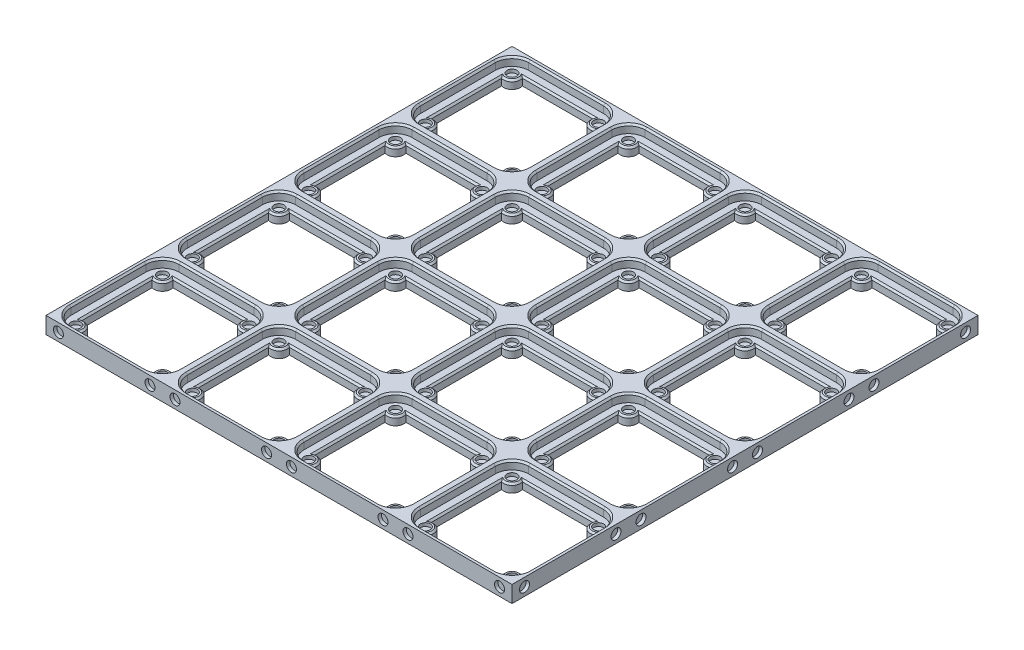
SolidWorks part; units mm, degrees
ref_plane "Front Plane" through (0, 0, 0) normal (0, 0, 1) x (1, 0, 0)
ref_plane "Top Plane" through (0, 0, 0) normal (0, 1, 0) x (1, 0, 0)
ref_plane "Right Plane" through (0, 0, 0) normal (1, 0, 0) x (0, 0, -1)
sketch "Sketch1" plane through (0, 0, 0) normal (0, 1, 0) x (1, 0, 0)
  line L1 (0, 0) -> (70, 0)
  line L2 (0, 0) -> (0, 70)
  line L3 (0, 70) -> (70, 70)
  line L4 (70, 0) -> (70, 70)
  dimension "D1" = 70
  dimension "D2" = 70
extrude "Boss-Extrude2" add sketch "Sketch1" along normal blind 7
sketch "Sketch3" plane through (0, 7, 0) normal (0, 1, 0) x (1, 0, 0)
  line L8 (2.5, 67.5) -> (2.5, 2.5)
  line L9 (2.5, 2.5) -> (67.5, 2.5)
  line L10 (67.5, 2.5) -> (67.5, 67.5)
  line L11 (67.5, 67.5) -> (2.5, 67.5)
  line L12 (2.5, 57.5) -> (2.5, 12.5)
  line L13 (12.5, 2.5) -> (57.5, 2.5)
  line L14 (67.5, 12.5) -> (67.5, 57.5)
  line L15 (57.5, 67.5) -> (12.5, 67.5)
  arc A0 (2.5, 12.5) -> (12.5, 2.5) centre (12.5, 12.5) ccw
  arc A1 (57.5, 2.5) -> (67.5, 12.5) centre (57.5, 12.5) ccw
  arc A2 (67.5, 57.5) -> (57.5, 67.5) centre (57.5, 57.5) ccw
  arc A3 (2.5, 57.5) -> (12.5, 67.5) centre (12.5, 57.5) cw
  dimension "D2" = 10
  dimension "D1" = 2.5
extrude "Cut-Extrude1" cut sketch "Sketch3" against normal blind 5
sketch "Sketch9" plane through (0, 0, 0) normal (0, -1, 0) x (1, 0, 0)
  line L1 (0, -70) -> (70, -70)
  line L2 (0, -70) -> (0, 0)
  line L3 (0, 0) -> (70, 0)
  line L4 (70, -70) -> (70, 0)
extrude "Boss-Extrude3" add sketch "Sketch9" along normal blind 5
sketch "Sketch20" plane through (0, 2, 0) normal (0, 1, 0) x (1, 0, 0)
  line L0 (35, 35) -> (8.9645, 61.0355) construction
  line L19 (12.5, 7.5) -> (57.5, 7.5)
  line L20 (62.5, 12.5) -> (62.5, 57.5)
  line L21 (57.5, 62.5) -> (12.5, 62.5)
  line L22 (7.5, 57.5) -> (7.5, 12.5)
  line L23 (13.7452, 7.5) -> (56.2548, 7.5)
  line L24 (62.5, 13.7452) -> (62.5, 56.2548)
  line L25 (56.2548, 62.5) -> (13.7452, 62.5)
  line L26 (7.5, 56.2548) -> (7.5, 13.7452)
  arc A0 (56.2548, 62.5) -> (62.5, 56.2548) centre (61.0355, 61.0355) ccw
  arc A1 (62.5, 13.7452) -> (56.2548, 7.5) centre (61.0355, 8.9645) ccw
  arc A2 (13.7452, 7.5) -> (7.5, 13.7452) centre (8.9645, 8.9645) ccw
  circle A4 centre (8.9645, 61.0355) radius 3
  circle A5 centre (8.9645, 8.9645) radius 3
  circle A6 centre (61.0355, 8.9645) radius 3
  circle A7 centre (61.0355, 61.0355) radius 3
  arc A21 (7.5, 56.2548) -> (13.7452, 62.5) centre (8.9645, 61.0355) ccw
  arc A24 (7.5, 12.5) -> (12.5, 7.5) centre (12.5, 12.5) ccw
  arc A25 (57.5, 7.5) -> (62.5, 12.5) centre (57.5, 12.5) ccw
  arc A26 (62.5, 57.5) -> (57.5, 62.5) centre (57.5, 57.5) ccw
  arc A27 (12.5, 62.5) -> (7.5, 57.5) centre (12.5, 57.5) ccw
  point P8 (35, 35)
  dimension "D2" = 6
  dimension "D3" = 4
  dimension "D4" = 36.8198
  dimension "D1" = 5
extrude "Cut-Extrude11" cut sketch "Sketch20" against normal through all contours L23 A1 L24 A0 L25 A21 L26 A2
sketch "Sketch21" plane through (0, 2, 0) normal (0, 1, 0) x (1, 0, 0)
  circle A0 centre (8.9645, 61.0355) radius 3
  circle A1 centre (61.0355, 61.0355) radius 3
  circle A2 centre (61.0355, 8.9645) radius 3
  circle A3 centre (8.9645, 8.9645) radius 3
extrude "Cut-Extrude12" cut sketch "Sketch21" against normal blind 2 contours A0 | A1 | A2 | A3
chamfer "Chamfer3" distance 1 angle 45 16 edges at (35, 7, -2.5) (64.5711, 7, -5.4289) (5.4289, 7, -5.4289) (67.5, 7, -35) (2.5, 7, -35) (64.5711, 7, -64.5711) (5.4289, 7, -64.5711) (35, 7, -67.5) (12.5, 2, -12.5) (35, 2, -7.5) (57.5, 2, -12.5) (62.5, 2, -35) (57.5, 2, -57.5) (7.5, 2, -35) (12.5, 2, -57.5) (35, 2, -62.5)
sketch "Sketch22" plane through (0, -5, 0) normal (0, -1, 0) x (1, 0, 0)
  line L0 (7.5, -13.7452) -> (7.5, -56.2548)
  line L1 (0, 0) -> (70, 0)
  line L2 (0, 0) -> (0, -70)
  line L3 (0, -70) -> (70, -70)
  line L4 (70, 0) -> (70, -70)
  line L6 (13.7452, -62.5) -> (56.2548, -62.5)
  line L8 (62.5, -56.2548) -> (62.5, -13.7452)
  line L10 (56.2548, -7.5) -> (13.7452, -7.5)
  arc A0 (7.5, -13.7452) -> (13.7452, -7.5) centre (8.9645, -8.9645) ccw
  arc A1 (56.2548, -7.5) -> (62.5, -13.7452) centre (61.0355, -8.9645) ccw
  arc A2 (62.5, -56.2548) -> (56.2548, -62.5) centre (61.0355, -61.0355) ccw
  arc A3 (13.7452, -62.5) -> (7.5, -56.2548) centre (8.9645, -61.0355) ccw
extrude "Cut-Extrude13" cut sketch "Sketch22" against normal blind 2
sketch "Sketch23" plane through (0, 0, 0) normal (-1, 0, 0) x (0, 0, 1)
  line L0 (-70, -3) -> (-70, 2)
  line L1 (-70, 7) -> (-70, -3) construction
  line L2 (-70, 2) -> (-62.5, 2)
  line L3 (-35, -3) -> (-35, 7)
  line L4 (0, -3) -> (-70, -3) construction
  line L5 (-70, 7) -> (0, 7) construction
  circle A0 centre (-62.5, 2) radius 3
  circle A1 centre (-7.5, 2) radius 3
extrude "Cut-Extrude14" cut sketch "Sketch23" against normal blind 2 contours A0 | A1 region at (0, -0.9151, -62.5) region at (0, 2, -7.5)
mirror "Mirror5" about plane through (0, 7, -70) normal (0, 0, 1) of bodies 138
mirror "Mirror6" about plane through (0, 7, -140) normal (0, 0, 1) of bodies 139
sketch "Sketch24" plane through (0, 0, 0) normal (0, 0, 1) x (1, 0, 0)
  line L0 (0, -3) -> (0, 2)
  line L1 (0, 7) -> (0, -3) construction
  line L2 (0, 2) -> (7.5, 2)
  line L3 (35, -3) -> (35, 7)
  line L4 (70, -3) -> (0, -3) construction
  line L5 (0, 7) -> (70, 7) construction
  circle A0 centre (7.5, 2) radius 3
  circle A1 centre (62.5, 2) radius 3
  dimension "D1" = 7.5
extrude "Cut-Extrude15" cut sketch "Sketch24" against normal blind 2 contours A0 | A1 region at (7.5, -0.9151, 0) region at (62.5, 2, 0)
ref_plane "Plane1" through (0, 0, -140) normal (0, 0, 1) x (1, 0, 0)
mirror "Mirror7" about plane through (0, 0, -140) normal (0, 0, 1) of "Cut-Extrude15"
mirror "Mirror9" about plane through (70, 7, 0) normal (-1, 0, 0) of bodies 142
sketch "Sketch25" plane through (138, 0, 0) normal (1, 0, 0) x (0, 0, -1)
  circle A0 centre (7.5, 2) radius 3
  circle A1 centre (62.5, 2) radius 3
  circle A2 centre (77.5, 2) radius 3
  circle A3 centre (132.5, 2) radius 3
  circle A4 centre (272.5, 2) radius 3
  circle A5 centre (217.5, 2) radius 3
  circle A6 centre (202.5, 2) radius 3
  circle A7 centre (147.5, 2) radius 3
extrude "Boss-Extrude4" add sketch "Sketch25" along normal blind 2
mirror "Mirror10" about plane through (140, 7, 0) normal (-1, 0, 0) of bodies 145
